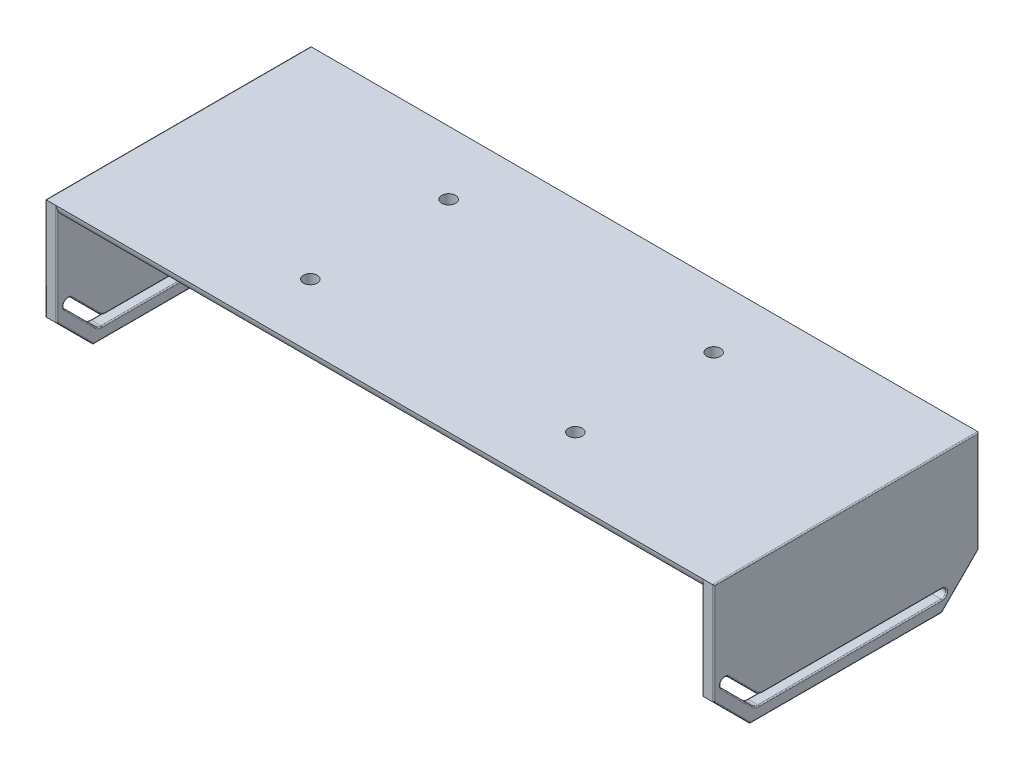
SolidWorks part; units mm, degrees
ref_plane "Płaszczyzna przednia" through (0, 0, 0) normal (0, 0, 1) x (1, 0, 0)
ref_plane "Płaszczyzna górna" through (0, 0, 0) normal (0, 1, 0) x (1, 0, 0)
ref_plane "Płaszczyzna prawa" through (0, 0, 0) normal (1, 0, 0) x (0, 0, -1)
sketch "Szkic1" plane through (0, 0, 0) normal (0, 1, 0) x (1, 0, 0)
  line L1 (-290, -115) -> (290, -115)
  line L2 (-290, -115) -> (-290, 115)
  line L3 (-290, 115) -> (290, 115)
  line L4 (290, -115) -> (290, 115)
  line L5 (-290, -115) -> (290, 115) construction
  line L6 (-290, 115) -> (290, -115) construction
  point P0 (0, 0)
  dimension "D1" = 580
  dimension "D2" = 230
extrude "Dodanie-wyciągnięcie1" add sketch "Szkic1" along normal blind 120
sketch "Szkic2" plane through (0, 0, 115) normal (0, 0, 1) x (1, 0, 0)
  line L0 (-290, 0) -> (290, 0) construction
  line L1 (-280, 0) -> (280, 0)
  line L2 (-280, 0) -> (-280, 110)
  line L3 (-280, 110) -> (280, 110)
  line L4 (280, 0) -> (280, 110)
  line L5 (-290, 120) -> (-290, 0) construction
  line L6 (290, 120) -> (290, 0) construction
  line L7 (-290, 120) -> (290, 120) construction
  dimension "D1" = 10
  dimension "D2" = 10
  dimension "D3" = 10
extrude "Wytnij-wyciągnięcie1" cut sketch "Szkic2" against normal through all
sketch "Szkic3" plane through (-290, 0, 0) normal (-1, 0, 0) x (0, 0, 1)
  line L0 (115, 31.8198) -> (83.1802, 0)
  line L1 (115, 120) -> (115, 0) construction
  line L2 (-115, 0) -> (115, 0) construction
  line L3 (0, -42.1939) -> (0, 179.0048) construction
  line L4 (-115, 31.8198) -> (-83.1802, 0)
  line L5 (83.1802, 0) -> (115, 0)
  line L6 (115, 0) -> (115, 31.8198)
  line L7 (-83.1802, 0) -> (-115, 0)
  line L8 (-115, 0) -> (-115, 31.8198)
  dimension "D1" = 45
  dimension "D2" = 45
extrude "Wytnij-wyciągnięcie2" cut sketch "Szkic3" against normal through all
sketch "Szkic4" plane through (-290, 0, 0) normal (-1, 0, 0) x (0, 0, 1)
  line L0 (115, 31.8198) -> (85.561, 61.2588) construction
  line L1 (115, 31.8198) -> (83.1802, 0) construction
  line L5 (79.0381, 10) -> (107.9289, 38.8909)
  line L6 (-83.1802, 10) -> (79.0381, 10)
  line L7 (81.3812, 12.3431) -> (107.9289, 38.8909)
  line L8 (-83.1802, 10) -> (75.7244, 10)
  line L12 (75.7244, 18) -> (102.2721, 44.5477)
  line L13 (-83.1802, 18) -> (75.7244, 18)
  line L14 (78.0675, 20.3431) -> (102.2721, 44.5477)
  line L15 (-83.1802, 18) -> (72.4106, 18)
  arc A0 (-83.1802, 18) -> (-83.1802, 10) centre (-83.1802, 14) ccw
  arc A1 (102.2721, 44.5477) -> (107.9289, 38.8909) centre (105.1005, 41.7193) cw
  arc A2 (81.3812, 12.3431) -> (75.7244, 10) centre (75.7244, 18) cw
  arc A3 (78.0675, 20.3431) -> (72.4106, 18) centre (72.4106, 26) cw
  point P20 (0, 0)
  point P21 (0, 0)
  dimension "D5" = 8
  dimension "D6" = 90
  dimension "D3" = 4
  dimension "D4" = 4
  dimension "D1" = 10
  dimension "D2" = 18
extrude "Wytnij-wyciągnięcie3" cut sketch "Szkic4" against normal through all
sketch "Szkic5" plane through (0, 120, 0) normal (0, 1, 0) x (1, 0, 0)
  line L1 (-115, -60) -> (115, -60) construction
  line L2 (-115, -60) -> (-115, 60) construction
  line L3 (-115, 60) -> (115, 60) construction
  line L4 (115, -60) -> (115, 60) construction
  line L5 (-115, -60) -> (115, 60) construction
  line L6 (-115, 60) -> (115, -60) construction
  point P0 (0, 0)
  dimension "D1" = 230
  dimension "D2" = 120
hole_wizard "Otwory ustalające Ø12.0mm1" positions "Szkic6" profile "Szkic7" hole size "Ø12.0" standard "ISO" end condition through all
sketch "Szkic6" plane through (0, 120, 0) normal (0, 1, 0) x (1, 0, 0)
  point P0 (-115, 60)
  point P3 (115, 60)
  point P6 (115, -60)
  point P9 (-115, -60)
sketch "Szkic7" plane through (-115, 120, -60) normal (1, 0, 0) x (0, 0, 1)
  line L0 (0, 0) -> (0, 120)
  line L1 (0, 120) -> (6, 120)
  line L2 (6, 120) -> (6, 0)
  line L5 (6, 0) -> (0, 0)
  line L11 (0, -6.35) -> (0, 107.95) construction
  dimension "Średnica otworu na wylot" = 12
  dimension "Głębokość otworu na wylot" = 120
fillet "Zaokrąglenie1" radius 10 2 edges at (0, 110, -115) (0, 110, 115)
fillet "Zaokrąglenie2" radius 1 53 edges at (-280, 44.5477, 107.9289) (-280, 25.617, 94.6551) (-280, 10.609, 78.7858) (-280, 10, -3.7279) (-280, 14, -87.1802) (-280, 18, -5.3848) (-280, 18.609, 75.4721) (280, 10, -3.7279) (280, 10.609, 78.7858) (280, 25.617, 94.6551) (280, 44.5477, 107.9289) (280, 32.4454, 90.1698) (280, 18.609, 75.4721) (280, 18, -5.3848) (290, 120, 0) (290, 75.9099, -115) (290, 15.9099, -99.0901) (290, 0, 0) (290, 15.9099, 99.0901) (290, 75.9099, 115) (290, 18.609, 75.4721) (290, 32.4454, 90.1698) (290, 44.5477, 107.9289) (290, 25.617, 94.6551) (290, 10.609, 78.7858) (290, 10, -3.7279) (290, 14, -87.1802) (290, 18, -5.3848) (-290, 15.9099, -99.0901) (-290, 75.9099, -115) (-290, 120, 0) (-290, 75.9099, 115) (-290, 15.9099, 99.0901) (-290, 0, 0) (-290, 10.609, 78.7858) (-290, 25.617, 94.6551) (-290, 44.5477, 107.9289) (-290, 32.4454, 90.1698) (-290, 18.609, 75.4721) (-290, 18, -5.3848) (-290, 14, -87.1802) (-290, 10, -3.7279) (-280, 32.4454, 90.1698) (280, 75.9099, 115) (280, 15.9099, 99.0901) (280, 75.9099, -115) (280, 15.9099, -99.0901) (280, 0, 0) (280, 14, -87.1802) (-280, 15.9099, -99.0901) (-280, 0, 0) (-280, 15.9099, 99.0901) (-280, 75.9099, 115)
